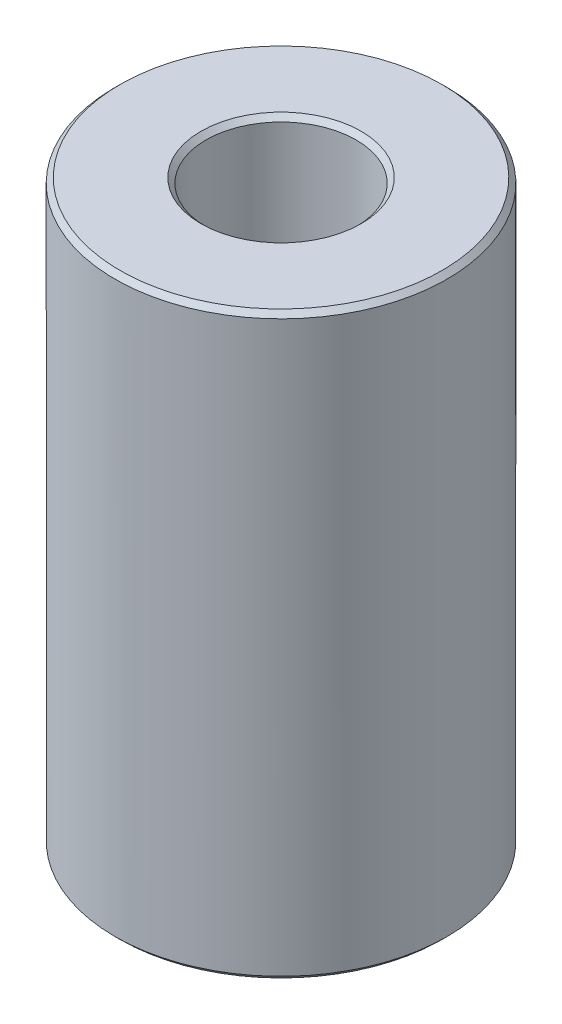
SolidWorks part; units mm, degrees
ref_plane "Front Plane" through (0, 0, 0) normal (0, 0, 1) x (1, 0, 0)
ref_plane "Top Plane" through (0, 0, 0) normal (0, 1, 0) x (1, 0, 0)
ref_plane "Right Plane" through (0, 0, 0) normal (1, 0, 0) x (0, 0, -1)
sketch "Sketch1" plane through (0, 0, 0) normal (0, 1, 0) x (1, 0, 0)
  circle A0 centre (0, 0) radius 22.5
  dimension "SLEEVE_OD" = 45
extrude "Boss-Extrude1" add sketch "Sketch1" along normal blind 78.5007
sketch "Sketch2" plane through (0, 0, 0) normal (0, 1, 0) x (1, 0, 0)
  circle A0 centre (0, 0) radius 10.1758
  dimension "BORE_D" = 20.3515
extrude "Cut-Extrude1" cut sketch "Sketch2" along normal through all
chamfer "Chamfer1" distance 0.679 angle 45 4 edges at (0, 78.5007, 10.1758) (0, 0, 10.1758) (0, 0, 22.5) (0, 78.5007, 22.5)
